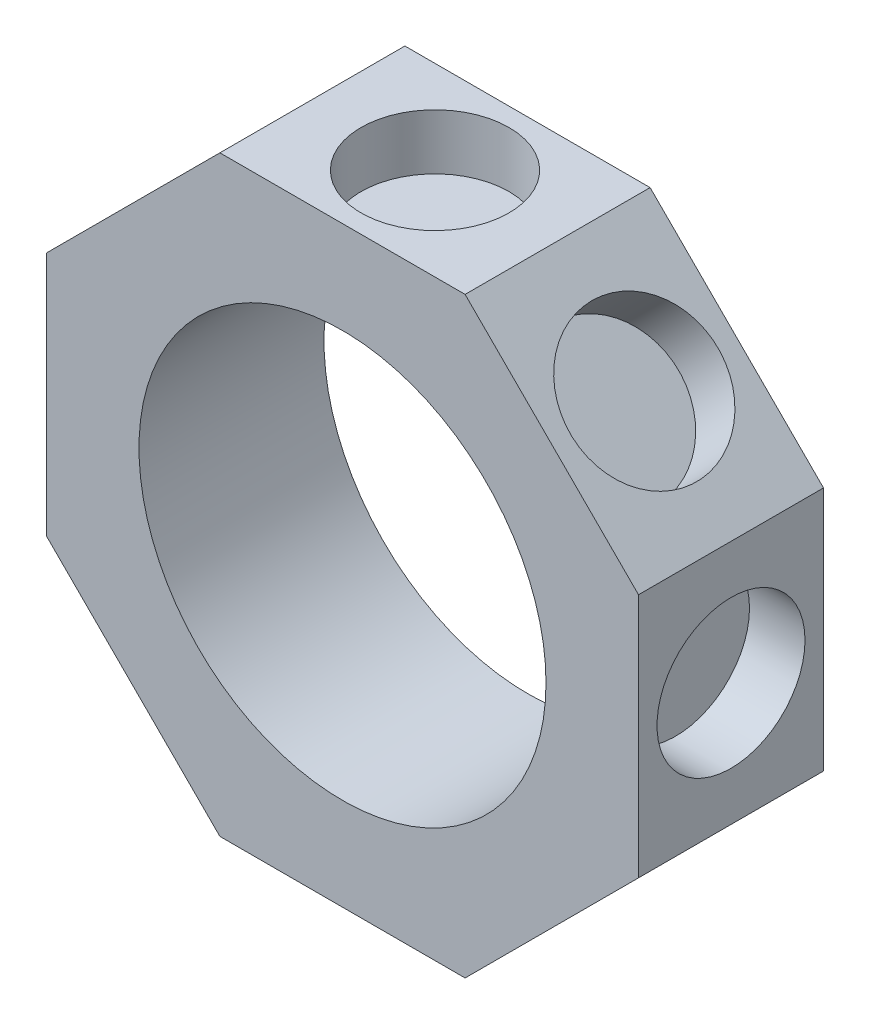
SolidWorks part; units mm, degrees
ref_plane "Top Plane" through (0, 0, 0) normal (0, 0, 1) x (1, 0, 0)
ref_plane "Right Plane" through (0, 0, 0) normal (0, 1, 0) x (1, 0, 0)
ref_plane "Front Plane" through (0, 0, 0) normal (1, 0, 0) x (0, 0, -1)
ref_axis "x-axis" through (-88.99, 0, 0) along (1, 0, 0)
ref_axis "y-axis" through (0, -55, 0) along (0, 1, 0)
ref_axis "z-axis" through (0, 0, 55) along (0, 0, -1)
sketch "Sketch1" plane through (0, 0, 0) normal (0, 0, 1) x (1, 0, 0)
  line L0 (6.6274, 16) -> (-6.6274, 16)
  line L1 (-16, 6.6274) -> (-16, -6.6274)
  line L2 (-16, -6.6274) -> (-6.6274, -16)
  line L3 (-6.6274, -16) -> (6.6274, -16)
  line L4 (6.6274, -16) -> (16, -6.6274)
  line L5 (16, -6.6274) -> (16, 6.6274)
  line L6 (16, 6.6274) -> (6.6274, 16)
  line L7 (-6.6274, 16) -> (-16, 6.6274)
  line L8 (-16, 0) -> (0, 0) construction
  circle A0 centre (0, 0) radius 11
  circle A1 centre (0, 0) radius 16 construction
  circle A2 centre (0, 0) radius 17.3183 construction
  dimension "D1" = 22
  dimension "D2" = 32
  dimension "D3" = 34.6366
extrude "Boss-Extrude1" add sketch "Sketch1" along normal mid plane 10
sketch "Sketch2" plane through (0, -16, 0) normal (0, -1, 0) x (-1, 0, 0)
  circle A0 centre (0, 0) radius 4
  dimension "D1" = 8
extrude "Cut-Extrude3" cut sketch "Sketch2" against normal blind 3
pattern_circular "CirPattern1" count 8 over 360 about axis through (0, 0, 5) along (0, 0, 1) of "Cut-Extrude3"
